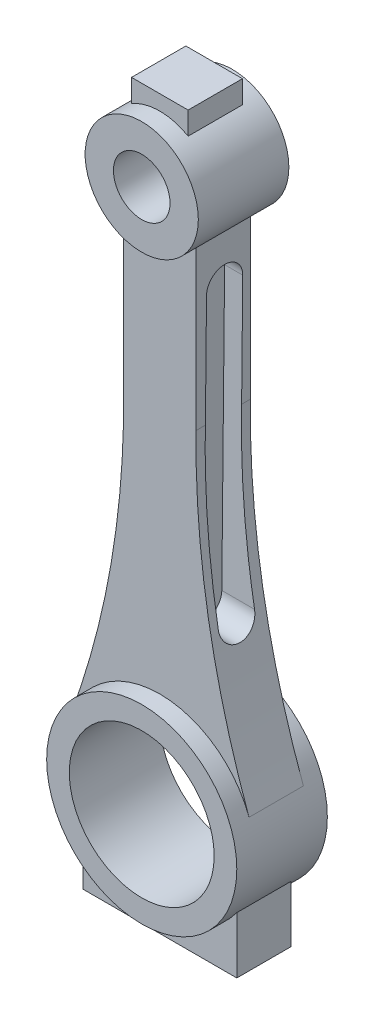
SolidWorks part; units mm, degrees
ref_plane "Front Plane" through (0, 0, 0) normal (0, 0, 1) x (1, 0, 0)
ref_plane "Top Plane" through (0, 0, 0) normal (0, 1, 0) x (1, 0, 0)
ref_plane "Right Plane" through (0, 0, 0) normal (1, 0, 0) x (0, 0, -1)
sketch "Sketch1" plane through (0, 0, 0) normal (0, 0, 1) x (1, 0, 0)
  line L0 (0, 138.8832) -> (0, -64.6789) construction
  line L1 (-8, 75.3953) -> (-8, 110.3953)
  line L2 (8, 75.3953) -> (8, 110.3953)
  line L3 (-6.25, 135.8253) -> (6.25, 135.8253)
  line L4 (6.25, 135.8253) -> (6.25, 130.8253)
  line L5 (-6.25, 135.8253) -> (-6.25, 130.8253)
  line L6 (-17, -24.8288) -> (-17, -12.3288)
  line L7 (-17, -24.8288) -> (17, -24.8288)
  line L8 (17, -24.8288) -> (17, -12.3288)
  circle A0 centre (0, 0) radius 21
  circle A1 centre (0, 0) radius 16
  circle A2 centre (0, 120) radius 6.25
  circle A3 centre (0, 120) radius 12.5
  arc A4 (-8, 75.3953) -> (-19.7046, 7.2614) centre (-197.9844, 72.9601) cw
  arc A5 (8, 75.3953) -> (19.7046, 7.2614) centre (197.9844, 72.9601) ccw
  point P19 (0, 135.8253)
  dimension "D1" = 120
  dimension "D2" = 42
  dimension "D3" = 32
  dimension "D4" = 25
  dimension "D5" = 12.5
  dimension "D6" = 8
  dimension "D8" = 190
  dimension "D7" = 35
  dimension "D9" = 12.5
  dimension "D10" = 5
  dimension "D11" = 5
  dimension "D12" = 12.5
  dimension "D13" = 34
  dimension "D14" = 12.5
extrude "Boss-Extrude2" add sketch "Sketch1" along normal mid plane 20 contours A3 L0 A2 | L0 A3 A2 | A0 L0 A1 | L0 A0 A1 region at (3.1629, 131.8041, 0) region at (-0.2795, 129.375, 0) region at (11.7421, 16.8411, 0) region at (-0.4696, 18.5, 0)
extrude "Boss-Extrude3" add sketch "Sketch1<7>" along normal mid plane 12 contours A3 L0 A0 A5 L2 | L0 A3 L1 A4 A0 | A0 L0 L7 L8 | L0 A0 L6 L7 | L3 L0 A3 L4 | L0 L3 L5 A3 region at (3.3472, 133.8599, 0) region at (-3.3472, 133.8599, 0) region at (-5.3241, 58.0487, 0) region at (5.3241, 58.0487, 0) region at (-10.2978, -21.1398, 0) region at (10.2978, -21.1398, 0)
sketch "Sketch1<7>" plane through (0, 0, 0) normal (0, 0, 1) x (1, 0, 0) same geometry as "Sketch1"
sketch "Sketch2" plane through (0, 0, 0) normal (1, 0, 0) x (0, 0, -1)
  line L0 (0.3106, 100) -> (-0.3106, 38) construction
  line L1 (4.3104, 99.9599) -> (3.6892, 37.9599)
  line L2 (-3.6892, 100.0401) -> (-4.3104, 38.0401)
  line L3 (10, 120) -> (-10, 120) construction
  line L4 (10, 107.5) -> (10, 132.5) construction
  line L5 (-10, 132.5) -> (-10, 107.5) construction
  arc A0 (4.3104, 99.9599) -> (-3.6892, 100.0401) centre (0.3106, 100) ccw
  arc A1 (-4.3104, 38.0401) -> (3.6892, 37.9599) centre (-0.3106, 38) ccw
  point P2 (0, 69)
  dimension "D2" = 4
  dimension "D1" = 62
  dimension "D3" = 20
extrude "Cut-Extrude1" cut sketch "Sketch2" against normal blind 2 and the other way through all from offset 6
mirror "Mirror1" about plane through (0, 0, 0) normal (1, 0, 0) of "Cut-Extrude1"
